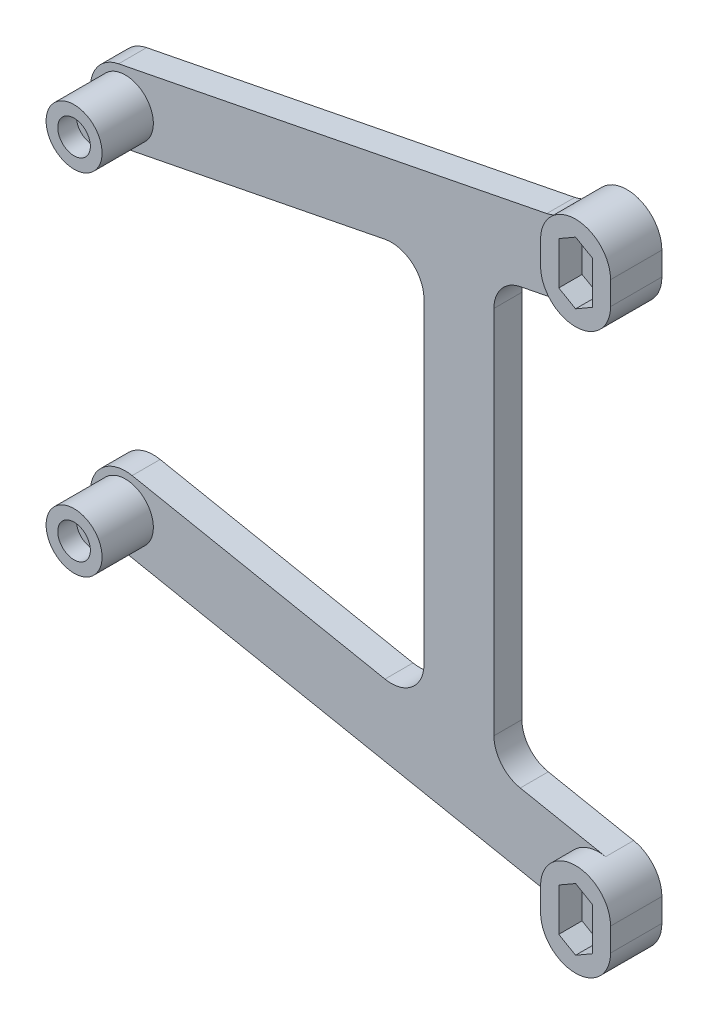
SolidWorks part; units mm, degrees
ref_plane "Front Plane" through (0, 0, 0) normal (0, 0, 1) x (1, 0, 0)
ref_plane "Top Plane" through (0, 0, 0) normal (0, 1, 0) x (1, 0, 0)
ref_plane "Right Plane" through (0, 0, 0) normal (1, 0, 0) x (0, 0, -1)
sketch "Sketch1" plane through (0, 0, 0) normal (0, 0, 1) x (1, 0, 0)
  line L58 (102.95, 87.6415) -> (84.6467, 84.0349)
  line L59 (90.3316, 100.4435) -> (-1.45, 82.3585)
  line L60 (55.6467, 78.3207) -> (1.45, 67.6415)
  line L83 (55.6467, -3.3207) -> (1.45, 7.3585)
  line L84 (79, 77.167) -> (79, -2.167)
  line L86 (64, 71.4527) -> (64, 3.5473)
  line L87 (102.6, -25) -> (102.6, -20)
  line L88 (100.4, -25) -> (100.4, -20)
  line L91 (109, 100) -> (109, 95)
  line L92 (100.4, 100) -> (100.4, 95)
  line L93 (109, -25) -> (109, -20)
  line L94 (90.3316, -25.4435) -> (-1.45, -7.3585)
  line L95 (102.6, 100) -> (102.6, 95)
  line L96 (102.95, -12.6415) -> (84.6467, -9.0349)
  circle A33 centre (0, 0) radius 3.5
  arc A42 (102.6, -25) -> (100.4, -25) centre (101.5, -25) cw
  arc A43 (100.4, -20) -> (102.6, -20) centre (101.5, -20) cw
  arc A48 (109, -20) -> (102.95, -12.6415) centre (101.5, -20) ccw
  arc A50 (95.0233, -28.7818) -> (109, -25) centre (101.5, -25) ccw
  arc A51 (1.45, 7.3585) -> (-1.45, -7.3585) centre (0, 0) ccw
  arc A52 (1.45, 67.6415) -> (-1.45, 82.3585) centre (0, 75) cw
  arc A53 (95.0233, 103.7818) -> (109, 100) centre (101.5, 100) cw
  arc A54 (109, 95) -> (102.95, 87.6415) centre (101.5, 95) cw
  arc A55 (100.4, 95) -> (102.6, 95) centre (101.5, 95) ccw
  arc A56 (102.6, 100) -> (100.4, 100) centre (101.5, 100) ccw
  circle A57 centre (0, 75) radius 3.5
  arc A58 (95.0233, -28.7818) -> (90.3316, -25.4435) centre (88.9783, -32.3115) ccw
  arc A59 (95.0233, 103.7818) -> (90.3316, 100.4435) centre (88.9783, 107.3115) cw
  arc A60 (64, 71.4527) -> (55.6467, 78.3207) centre (57, 71.4527) ccw
  arc A61 (79, 77.167) -> (84.6467, 84.0349) centre (86, 77.167) cw
  arc A62 (64, 3.5473) -> (55.6467, -3.3207) centre (57, 3.5473) cw
  arc A63 (79, -2.167) -> (84.6467, -9.0349) centre (86, -2.167) ccw
  point P44 (0, 0)
  point P47 (0, 0)
extrude "Boss-Extrude1" add sketch "Sketch1" along normal blind 6
sketch "Sketch2" plane through (0, 0, 6) normal (0, 0, 1) x (1, 0, 0)
  circle A0 centre (0, 75) radius 6
  circle A1 centre (0, 75) radius 3.5
  circle A2 centre (0, 0) radius 3.5
  circle A3 centre (0, 0) radius 6
extrude "Boss-Extrude2" add sketch "Sketch2" along normal blind 11
sketch "Sketch3" plane through (0, 0, 0) normal (0, 0, -1) x (-1, 0, 0)
  circle A0 centre (0, 75) radius 3.5
  circle A1 centre (0, 75) radius 1.65
  circle A2 centre (0, 0) radius 3.5
  circle A3 centre (0, 0) radius 1.65
extrude "Boss-Extrude3" add sketch "Sketch3" against normal offset from surface (8 mm away) 4 from offset 5 up to face at (6, 75, 17) offset against normal yes
sketch "Sketch4" plane through (0, 0, 6) normal (0, 0, 1) x (1, 0, 0)
  line L2 (94, -20) -> (94, -25)
  line L4 (109, -20) -> (109, -25)
  line L6 (94, 100) -> (94, 95)
  line L8 (109, 100) -> (109, 95)
  line L9 (101.5, -15.8431) -> (97.9, -17.9215)
  line L14 (105.1, -17.9215) -> (101.5, -15.8431)
  line L17 (97.9, -27.0785) -> (101.5, -29.1569)
  line L18 (101.5, -29.1569) -> (105.1, -27.0785)
  line L21 (101.5, 104.1569) -> (97.9, 102.0785)
  line L26 (105.1, 102.0785) -> (101.5, 104.1569)
  line L29 (97.9, 92.9215) -> (101.5, 90.8431)
  line L30 (101.5, 90.8431) -> (105.1, 92.9215)
  line L34 (97.9, 102.0785) -> (97.9, 92.9215)
  line L36 (105.1, 102.0785) -> (105.1, 92.9215)
  line L38 (97.9, -17.9215) -> (97.9, -27.0785)
  line L40 (105.1, -17.9215) -> (105.1, -27.0785)
  arc A0 (109, 100) -> (94, 100) centre (101.5, 100) ccw
  arc A1 (94, 95) -> (109, 95) centre (101.5, 95) ccw
  arc A2 (109, -20) -> (94, -20) centre (101.5, -20) ccw
  arc A3 (94, -25) -> (109, -25) centre (101.5, -25) ccw
extrude "Boss-Extrude4" add sketch "Sketch4" along normal blind 5
